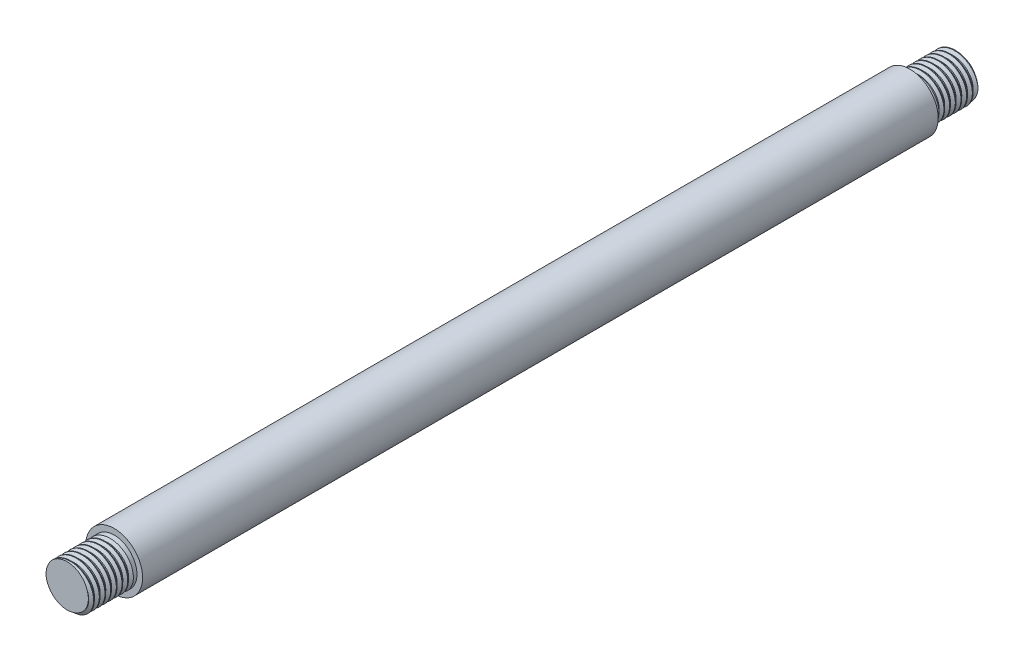
SolidWorks part; units mm, degrees
ref_plane "Front Plane" through (0, 0, 0) normal (0, 0, 1) x (1, 0, 0)
ref_plane "Top Plane" through (0, 0, 0) normal (0, 1, 0) x (1, 0, 0)
ref_plane "Right Plane" through (0, 0, 0) normal (1, 0, 0) x (0, 0, -1)
sketch "Sketch1" plane through (0, 0, 0) normal (0, 0, 1) x (1, 0, 0)
  line L0 (0, 0) -> (0, 50000) construction
  line L1 (0, 0) -> (50000, 0) construction
  circle A0 centre (0, 0) radius 5
  circle A1 centre (0, 0) radius 4
extrude "Boss-Extrude1" add sketch "Sketch1" along normal mid plane 156 contours A1 region at (0, 0, 0)
extrude "Boss-Extrude2" add sketch "Sketch1<3>" along normal mid plane 140
sketch "Sketch1<3>" plane through (0, 0, 0) normal (0, 0, 1) x (1, 0, 0) same geometry as "Sketch1"
thread "Thread1" pitch 1 method cut profile "Thread Profile1" start angle 0, offset 1, length 8, pitch 1, diameter 8
ref_plane "Plane1" through (-4, 0, 79) normal (0, -1, 0) x (-1, 0, 0)
sketch "Thread Profile1" plane through (-4, 0, 79) normal (0, -1, 0) x (-1, 0, 0)
  line L0 (0, 0) -> (0, 1) construction
  line L11 (0, 0) -> (0, 0.875)
  line L12 (0, 0.875) -> (-0.5413, 0.5625)
  line L13 (-0.5413, 0.5625) -> (-0.5413, 0.3125)
  line L15 (-0.5413, 0.3125) -> (0, 0)
  line L17 (-0.5413, 0.4375) -> (0, 0.4375) construction
  point P2 (0, 0)
  dimension "Pitch" = 1
  dimension "Profile_Angle" = 60
  dimension "Profile_Land" = 0.25
  dimension "Profile_Height" = 0.5413
thread "Thread2" pitch 1 method cut profile "Thread Profile2" start angle 0, offset 1, length 8, pitch 1, diameter 8
ref_plane "Plane2" through (4, 0, -79) normal (0, -1, 0) x (1, 0, 0)
sketch "Thread Profile2" plane through (4, 0, -79) normal (0, -1, 0) x (1, 0, 0)
  line L0 (0, 0) -> (0, 1) construction
  line L11 (0, 0) -> (0, 0.875)
  line L12 (0, 0.875) -> (-0.5413, 0.5625)
  line L13 (-0.5413, 0.5625) -> (-0.5413, 0.3125)
  line L15 (-0.5413, 0.3125) -> (0, 0)
  line L17 (-0.5413, 0.4375) -> (0, 0.4375) construction
  point P2 (0, 0)
  dimension "Pitch" = 1
  dimension "Profile_Angle" = 60
  dimension "Profile_Land" = 0.25
  dimension "Profile_Height" = 0.5413
